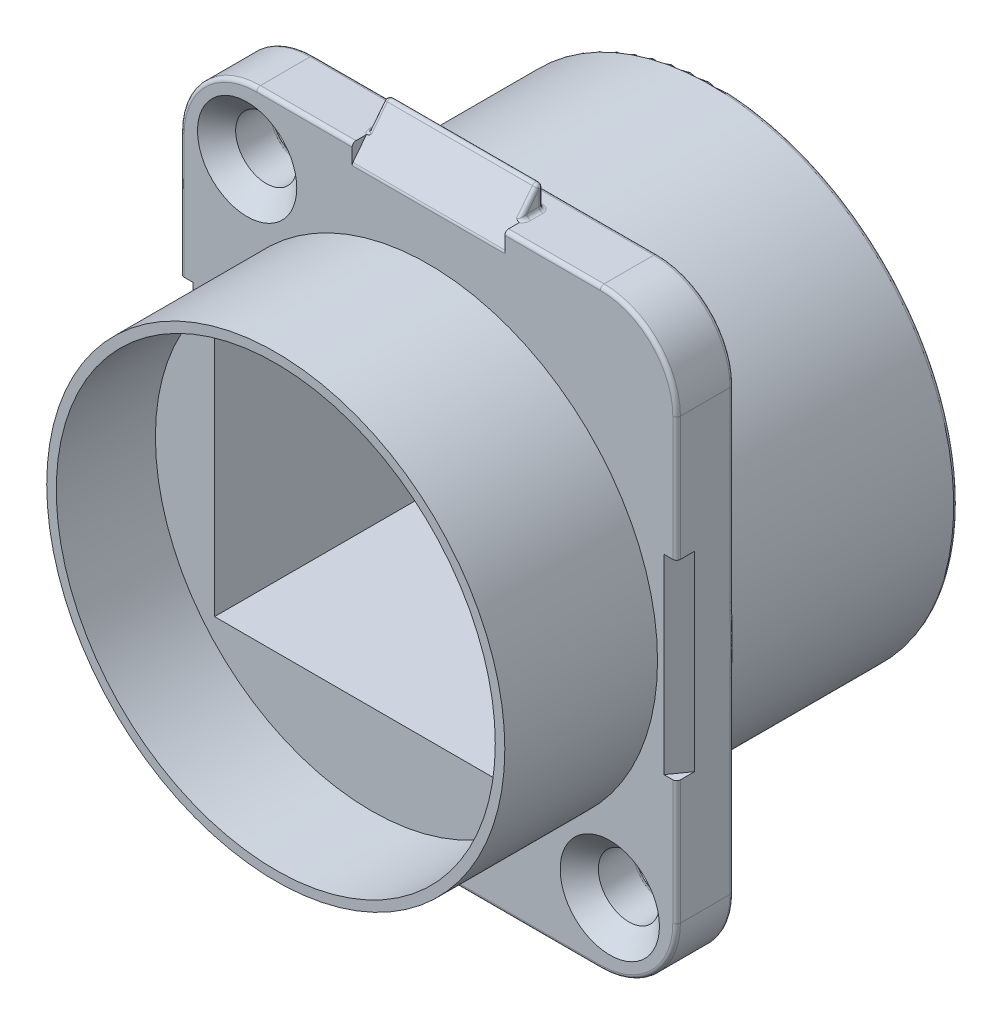
SolidWorks part; units mm, degrees
ref_plane "Front Plane" through (0, 0, 0) normal (0, 0, 1) x (1, 0, 0)
ref_plane "Top Plane" through (0, 0, 0) normal (0, 1, 0) x (1, 0, 0)
ref_plane "Right Plane" through (0, 0, 0) normal (1, 0, 0) x (0, 0, -1)
sketch "Sketch1" plane through (0, 0, 0) normal (0, 0, 1) x (1, 0, 0)
  line L0 (0, 25.3515) -> (0, -23.7313) construction
  line L1 (-13, 15.5) -> (13, 15.5)
  line L2 (-13, 15.5) -> (-13, -15.5)
  line L3 (-13, -15.5) -> (13, -15.5)
  line L4 (13, 15.5) -> (13, -15.5)
  line L5 (-25.8534, 0) -> (43.6508, 0) construction
  circle A0 centre (0, 0) radius 12
  circle A1 centre (-9.5, 12) radius 1.6
  circle A2 centre (9.5, -12) radius 1.6
  point P0 (0, 0)
  dimension "D3" = 24
  dimension "D4" = 3.2
  dimension "D5" = 3.2
  dimension "D7" = 9.5
  dimension "D1" = 26
  dimension "D2" = 31
  dimension "D6" = 9.5
  dimension "D8" = 12
  dimension "D9" = 12
extrude "Boss-Extrude1" add sketch "Sketch1" against normal blind 2
sketch "Sketch4" plane through (0, 0, -2) normal (0, 0, -1) x (-1, 0, 0)
  circle A0 centre (0, 0) radius 12 construction
  circle A1 centre (0, 0) radius 12
extrude "Boss-Extrude2" add sketch "Sketch4" against normal blind 10
chamfer "Chamfer at Holes" distance 1 angle 45 2 edges at (-7.9, 12, 0) (11.1, -12, 0)
fillet "Fillet1" radius 4 4 edges at (13, 15.5, -1) (-13, 15.5, -1) (-13, -15.5, -1) (13, -15.5, -1)
sketch "Sketch5" plane through (0, 0, 8) normal (0, 0, 1) x (1, 0, 0)
  circle A0 centre (0, 0) radius 11.5
  circle A1 centre (0, 0) radius 12 construction
  dimension "D1" = 0.5
extrude "Cut-Extrude1" cut sketch "Sketch5" against normal up to surface (8 mm away) up to face at (-6.9, 12, 0)
sketch "Sketch7" plane through (0, 0, -2) normal (0, 0, -1) x (-1, 0, 0)
  line L4 (9, 15.5) -> (-9, 15.5)
  line L5 (-13, 11.5) -> (-13, -11.5)
  line L6 (-9, -15.5) -> (9, -15.5)
  line L7 (13, -11.5) -> (13, 11.5)
  line L8 (9, 15.5) -> (-9, 15.5)
  line L9 (-13, 11.5) -> (-13, -11.5)
  line L10 (-9, -15.5) -> (9, -15.5)
  line L11 (13, -11.5) -> (13, 11.5)
  circle A0 centre (-9.5, -12) radius 1.6 construction
  circle A1 centre (9.5, 12) radius 1.6 construction
  circle A2 centre (-9.5, -12) radius 1.6
  circle A3 centre (9.5, 12) radius 1.6
  arc A4 (-9, 15.5) -> (-13, 11.5) centre (-9, 11.5) ccw
  arc A5 (-13, -11.5) -> (-9, -15.5) centre (-9, -11.5) ccw
  arc A6 (9, -15.5) -> (13, -11.5) centre (9, -11.5) ccw
  arc A7 (13, 11.5) -> (9, 15.5) centre (9, 11.5) ccw
  arc A8 (-9, 15.5) -> (-13, 11.5) centre (-9, 11.5) ccw
  arc A9 (-13, -11.5) -> (-9, -15.5) centre (-9, -11.5) ccw
  arc A10 (9, -15.5) -> (13, -11.5) centre (9, -11.5) ccw
  arc A11 (13, 11.5) -> (9, 15.5) centre (9, 11.5) ccw
  dimension "D1" = 0
extrude "Boss-Extrude5" add sketch "Sketch7" along normal blind 1 separate body
sketch "Sketch8" plane through (0, 0, -3) normal (0, 0, -1) x (-1, 0, 0)
  circle A0 centre (0, 0) radius 12.716
extrude "Boss-Extrude6" add sketch "Sketch8" along normal blind 12
sketch "Sketch11" plane through (0, 0, 0) normal (0, 0, 1) x (1, 0, 0)
  circle A0 centre (0, 0) radius 11.3069
extrude "Boss-Extrude7" add sketch "Sketch11" along normal blind 3
sketch "Sketch13" plane through (0, 0, 3) normal (0, 0, 1) x (1, 0, 0)
  line L1 (-8.205, 6.6) -> (8.205, 6.6)
  line L2 (-8.205, 6.6) -> (-8.205, -6.6)
  line L3 (-8.205, -6.6) -> (8.205, -6.6)
  line L4 (8.205, 6.6) -> (8.205, -6.6)
  line L5 (-8.205, 6.6) -> (8.205, -6.6) construction
  line L6 (-8.205, -6.6) -> (8.205, 6.6) construction
  point P0 (0, 0)
  dimension "D1" = 16.41
  dimension "D2" = 13.2
extrude "Cut-Extrude2" cut sketch "Sketch13" against normal blind 15.6
sketch "Sketch14" plane through (0, 0, -15) normal (0, 0, -1) x (-1, 0, 0)
  line L1 (-8.205, 6.6) -> (8.205, 6.6)
  line L2 (-8.205, 6.6) -> (-8.205, -6.6)
  line L3 (-8.205, -6.6) -> (8.205, -6.6)
  line L4 (8.205, 6.6) -> (8.205, -6.6)
  line L5 (-8.205, 6.6) -> (8.205, -6.6) construction
  line L6 (-8.205, -6.6) -> (8.205, 6.6) construction
  point P0 (0, 0)
  dimension "D1" = 16.41
  dimension "D2" = 13.2
extrude "Cut-Extrude3" cut sketch "Sketch14" against normal blind 2
ref_plane "Horizontal Plane" through (0, 0, 0) normal (0, -1, 0) x (-1, 0, 0)
ref_plane "Vertical Plane" through (0, 0, 0) normal (-1, 0, 0) x (0, 0, 1)
sketch "Sketch15" plane through (0, 0, 0) normal (0, -1, 0) x (-1, 0, 0)
  line L0 (12.3343, 0) -> (13, 0.9378)
  line L2 (13, 2) -> (13, 0) construction
  line L3 (-13, 0.9378) -> (-13, 0)
  line L4 (13, 0) -> (12.3343, 0)
  line L5 (9, 0) -> (13, 0) construction
  line L6 (13, 0.9378) -> (13, 0)
  line L7 (0, -4.2861) -> (0, 7.3309) construction
  line L8 (-13, 0) -> (-12.3343, 0)
  line L9 (-12.3343, 0) -> (-13, 0.9378)
  point P0 (12.3343, 0)
extrude "Cut-Extrude4" cut sketch "Sketch15" against normal mid plane 10
sketch "Sketch18" plane through (0, 0, 0) normal (-1, 0, 0) x (0, 0, 1)
  line L0 (-2, 15.5) -> (0, 15.5) construction
  line L1 (-2, 15.5) -> (0, 15.5)
  line L2 (0, 15.5) -> (0, 14.5915)
  line L3 (-2, 15.5) -> (-2, 14.5915)
  line L4 (-2, 14.5915) -> (0, 14.5915)
extrude "Cut-Extrude5" cut sketch "Sketch18" against normal mid plane 8
sketch "Sketch19" plane through (0, 0, 0) normal (-1, 0, 0) x (0, 0, 1)
  line L2 (-2, 15.5) -> (-2, 17.0971)
  line L3 (-2, 17.0971) -> (0, 14.5356)
  line L4 (0, 14.5356) -> (-2, 14.5356)
  line L5 (-2, 14.5356) -> (-2, 15.5)
extrude "Boss-Extrude8" add sketch "Sketch19" along normal mid plane 8
fillet "Fillet2" radius 0.2 12 edges at (-13, 8.25, 0) (-11.8284, 14.3284, 0) (13, 8.25, 0) (11.8284, 14.3284, 0) (4, 16.2986, -2) (4, 16.2986, -1.3765) (-4, 16.2986, -1.3765) (-4, 16.2986, -2) (-6.5, 15.5, 0) (6.5, 15.5, 0) (0, 14.5915, 0) (0, 17.0971, -2)
fillet "Fillet3" radius 0.2 7 edges at (-3.9414, 15.5, -0.8273) (-4, 15.5, -1.4034) (-3.9414, 15.5, -1.9414) (3.9414, 15.5, -0.8273) (4, 15.5, -1.4034) (3.9414, 15.5, -1.9414) (0, 15.5, -2)
fillet "Fillet4" radius 0.2 2 edges at (-12.716, 0, -3) (-12.716, 0, -15)
fillet "Fillet5" radius 0.2 5 edges at (-13, -8.25, 0) (-11.8284, -14.3284, 0) (0, -15.5, 0) (13, -8.25, 0) (11.8284, -14.3284, 0)
fillet "Fillet6" radius 0.2 10 edges at (-11.1, 12, -3) (-13, 0, -3) (-11.8284, -14.3284, -3) (0, -15.5, -3) (11.8284, -14.3284, -3) (13, 0, -3) (11.8284, 14.3284, -3) (0, 15.5, -3) (-11.8284, 14.3284, -3) (7.9, -12, -3)
